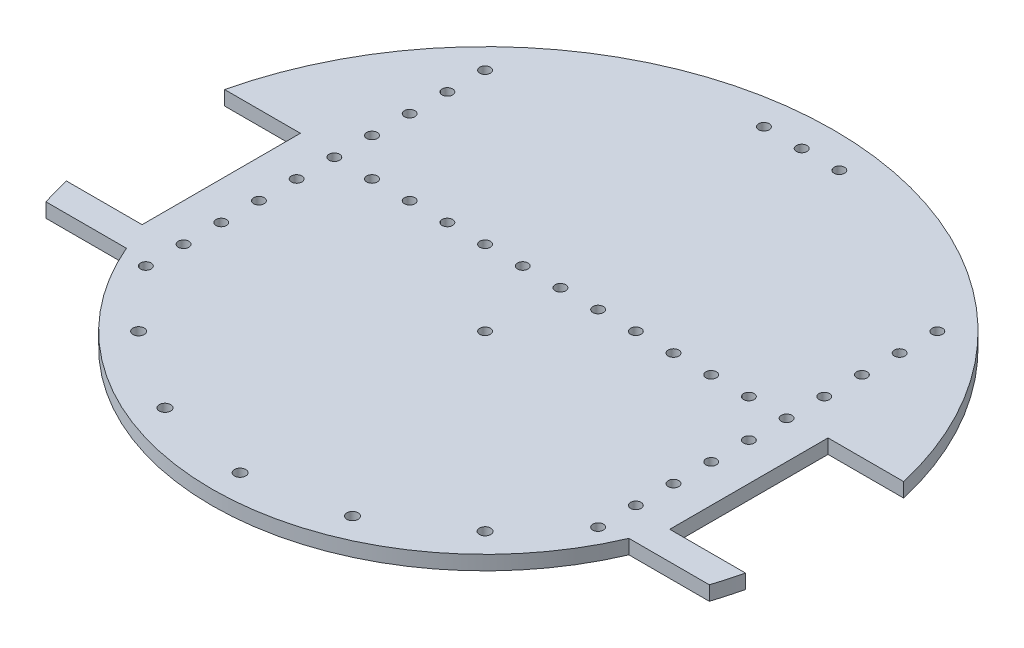
SolidWorks part; units mm, degrees
material "Balsa"
ref_plane "Front Plane" through (0, 0, 0) normal (0, 0, 1) x (1, 0, 0)
ref_plane "Top Plane" through (0, 0, 0) normal (0, 1, 0) x (1, 0, 0)
ref_plane "Right Plane" through (0, 0, 0) normal (1, 0, 0) x (0, 0, -1)
sketch "Sketch1" plane through (0, 0, 0) normal (0, 1, 0) x (1, 0, 0)
  circle A0 centre (0, 0) radius 117.475
  dimension "D1" = 234.95
extrude "Boss-Extrude1" add sketch "Sketch1" against normal blind 4.826
sketch "Sketch3" plane through (0, 0, 0) normal (0, 1, 0) x (1, 0, 0)
  line L1 (-114.4075, 26.67) -> (-88.9, 26.67)
  line L2 (0, -92.075) -> (0, -117.475)
  line L3 (-88.9, -26.67) -> (-88.9, 26.67)
  line L4 (0, 0) -> (-88.9, 0) construction
  line L5 (0, 0) -> (0, -117.475) construction
  line L6 (0, 0) -> (0, 117.475) construction
  line L8 (-88.9, -26.67) -> (-114.4075, -26.67)
  line L10 (-84.6624, -36.195) -> (-111.76, -36.195)
  arc A0 (-114.4075, 26.67) -> (-114.4075, -26.67) centre (0, 0) ccw
  circle A1 centre (0, 0) radius 117.475 construction
  arc A3 (-84.6624, -36.195) -> (0, -92.075) centre (0, 0) ccw
  arc A4 (-111.76, -36.195) -> (0, -117.475) centre (0, 0) ccw
  dimension "D1" = 88.9
  dimension "D2" = 53.34
  dimension "D4" = 9.525
  dimension "D5" = 25.4
extrude "Cut-Extrude4" cut sketch "Sketch3" against normal through all
sketch "Sketch4" plane through (0, 0, 0) normal (0, 1, 0) x (1, 0, 0)
  line L0 (-76.2, 38.1) -> (-76.2, 25.4) construction
  line L1 (-76.2, 25.4) -> (-76.2, 12.7) construction
  line L2 (-76.2, 12.7) -> (-76.2, 0) construction
  line L3 (-76.2, 0) -> (-76.2, -12.7) construction
  line L4 (-76.2, -12.7) -> (-76.2, -25.4) construction
  line L5 (-76.2, -25.4) -> (-76.2, -38.1) construction
  line L6 (0, 0) -> (-76.2, 0) construction
  line L7 (-76.2, -12.7) -> (-88.9, -12.7) construction
  line L11 (-88.9, -26.67) -> (-88.9, 26.67) construction
  line L12 (-76.2, 76.2) -> (-76.2, 63.5) construction
  line L13 (-76.2, 63.5) -> (-76.2, 50.8) construction
  line L14 (-76.2, 50.8) -> (-76.2, 38.1) construction
  circle A0 centre (-76.2, 0) radius 1.778
  circle A1 centre (-76.2, 12.7) radius 1.778
  circle A2 centre (-76.2, 25.4) radius 1.778
  circle A3 centre (-76.2, 38.1) radius 1.778
  circle A4 centre (-76.2, -12.7) radius 1.778
  circle A5 centre (-76.2, -25.4) radius 1.778
  circle A6 centre (-76.2, -38.1) radius 1.778
  circle A7 centre (-76.2, 50.8) radius 1.778
  circle A8 centre (-76.2, 63.5) radius 1.778
  circle A9 centre (-76.2, 76.2) radius 1.778
  dimension "D2" = 3.556
  dimension "D1" = 12.7
  dimension "D3" = 76.2
extrude "Cut-Extrude5" cut sketch "Sketch4" against normal through all
sketch "Sketch5" plane through (0, 0, 0) normal (0, 1, 0) x (1, 0, 0)
  circle A0 centre (0, 0) radius 1.778
  dimension "D1" = 3.556
extrude "Cut-Extrude6" cut sketch "Sketch5" against normal through all
sketch "Sketch6" plane through (0, 0, 0) normal (0, 1, 0) x (1, 0, 0)
  line L0 (0, 0) -> (0, 25.4) construction
  line L1 (0, 25.4) -> (12.7, 25.4) construction
  line L2 (12.7, 25.4) -> (25.4, 25.4) construction
  line L3 (25.4, 25.4) -> (38.1, 25.4) construction
  line L4 (-38.1, 25.4) -> (-50.8, 25.4) construction
  line L5 (38.1, 25.4) -> (50.8, 25.4) construction
  line L6 (0, 25.4) -> (-12.7, 25.4) construction
  line L7 (-12.7, 25.4) -> (-25.4, 25.4) construction
  line L8 (-25.4, 25.4) -> (-38.1, 25.4) construction
  line L9 (-50.8, 25.4) -> (-63.5, 25.4) construction
  line L10 (50.8, 25.4) -> (63.5, 25.4) construction
  line L11 (0, 106.68) -> (12.7, 106.68) construction
  line L12 (12.7, 106.68) -> (25.4, 106.68) construction
  line L13 (25.4, 106.68) -> (38.1, 106.68) construction
  line L14 (-38.1, 106.68) -> (-50.8, 106.68) construction
  line L15 (38.1, 106.68) -> (50.8, 106.68) construction
  line L16 (0, 106.68) -> (-12.7, 106.68) construction
  line L17 (-12.7, 106.68) -> (-25.4, 106.68) construction
  line L18 (-25.4, 106.68) -> (-38.1, 106.68) construction
  line L19 (-50.8, 106.68) -> (-63.5, 106.68) construction
  line L20 (50.8, 106.68) -> (63.5, 106.68) construction
  line L21 (0, 25.4) -> (0, 106.68) construction
  circle A0 centre (0, 25.4) radius 1.778
  circle A1 centre (-12.7, 25.4) radius 1.778
  circle A2 centre (-25.4, 25.4) radius 1.778
  circle A3 centre (-38.1, 25.4) radius 1.778
  circle A4 centre (12.7, 25.4) radius 1.778
  circle A5 centre (25.4, 25.4) radius 1.778
  circle A6 centre (38.1, 25.4) radius 1.778
  circle A7 centre (-50.8, 25.4) radius 1.778
  circle A8 centre (50.8, 25.4) radius 1.778
  circle A9 centre (-63.5, 25.4) radius 1.778
  circle A10 centre (63.5, 25.4) radius 1.778
  circle A11 centre (0, 106.68) radius 1.778
  circle A12 centre (-12.7, 106.68) radius 1.778
  circle A13 centre (-25.4, 106.68) radius 1.778 construction
  circle A14 centre (-38.1, 106.68) radius 1.778 construction
  circle A15 centre (12.7, 106.68) radius 1.778
  circle A16 centre (25.4, 106.68) radius 1.778 construction
  circle A17 centre (38.1, 106.68) radius 1.778 construction
  circle A18 centre (-50.8, 106.68) radius 1.778 construction
  circle A19 centre (50.8, 106.68) radius 1.778 construction
  circle A20 centre (-63.5, 106.68) radius 1.778 construction
  circle A21 centre (63.5, 106.68) radius 1.778 construction
  dimension "D1" = 3.556
  dimension "D4" = 3.556
  dimension "D2" = 12.7
  dimension "D3" = 25.4
  dimension "D5" = 12.7
  dimension "D6" = 81.28
extrude "Cut-Extrude7" cut sketch "Sketch6" against normal through all
sketch "Sketch7" plane through (0, 0, 0) normal (0, 1, 0) x (1, 0, 0)
  line L0 (-8.9803, 8.9803) -> (0, 0) construction
  line L1 (0, 0) -> (8.9803, -8.9803) construction
  line L3 (8.9803, 8.9803) -> (0, 0) construction
  line L4 (0, 0) -> (-8.9803, -8.9803) construction
  line L6 (-12.7, 0) -> (0, 0) construction
  line L7 (0, 0) -> (0, 12.7) construction
  line L9 (12.7, 0) -> (0, 0) construction
  line L10 (0, 0) -> (0, -12.7) construction
  circle A0 centre (0, 12.7) radius 1.778
  circle A1 centre (12.7, 0) radius 1.778
  circle A2 centre (0, -12.7) radius 1.778
  circle A3 centre (-12.7, 0) radius 1.778
  circle A4 centre (-8.9803, 8.9803) radius 1.778
  circle A5 centre (8.9803, 8.9803) radius 1.778
  circle A6 centre (8.9803, -8.9803) radius 1.778
  circle A7 centre (-8.9803, -8.9803) radius 1.778
  dimension "D1" = 45
  dimension "D2" = 3.556
  dimension "D3" = 12.7
extrude "Cut-Extrude8" [suppressed] cut sketch "Sketch7" against normal through all
sketch "Sketch8" plane through (0, 0, 0) normal (0, 1, 0) x (1, 0, 0)
  line L0 (0, 0) -> (-35.921, -35.921) construction
  line L1 (-35.921, -35.921) -> (-35.921, -1.2798) construction
  circle A0 centre (-35.921, -35.921) radius 12.7
  dimension "D3" = 25.4
  dimension "D1" = 45
  dimension "D2" = 50.8
extrude "Cut-Extrude9" [suppressed] cut sketch "Sketch8" against normal through all
mirror "Mirror1" about plane through (0, 0, 0) normal (1, 0, 0) of "Cut-Extrude4"
mirror "Mirror3" about plane through (0, 0, 0) normal (1, 0, 0) of "Cut-Extrude5"
sketch "Sketch9" plane through (0, 0, 0) normal (0, 1, 0) x (1, 0, 0)
  line L4 (0, -82.55) -> (0, 0) construction
  circle A1 centre (0, -82.55) radius 1.905
  dimension "D2" = 3.81
  dimension "D1" = 82.55
extrude "Cut-Extrude10" cut sketch "Sketch9" against normal through all
pattern_circular "CirPattern1" count 3 over 45 about axis through (0, -4.826, 0) along (0, 1, 0) of "Cut-Extrude10"
pattern_circular "CirPattern2" count 3 over 45 about axis through (0, -4.826, 0) along (0, 1, 0) of "Cut-Extrude10" reverse direction yes
sketch "Sketch10" plane through (0, 0, 0) normal (0, 1, 0) x (1, 0, 0)
  line L0 (-19.812, 85.09) -> (-19.812, 0) construction
  line L1 (-19.812, 0) -> (0, 0) construction
  circle A0 centre (-19.812, 85.09) radius 15.875
  dimension "D1" = 31.75
  dimension "D2" = 85.09
  dimension "D3" = 19.812
extrude "Cut-Extrude11" [suppressed] cut sketch "Sketch10" against normal through all
